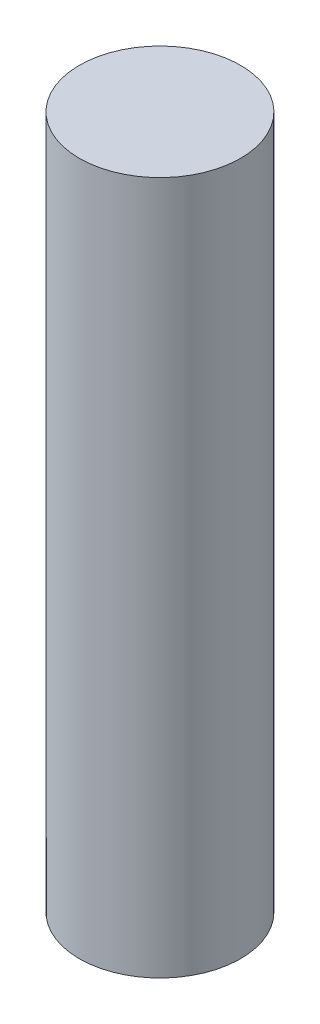
SolidWorks part; units mm, degrees
material "Plain Carbon Steel"
ref_plane "Front Plane" through (0, 0, 0) normal (0, 0, 1) x (1, 0, 0)
ref_plane "Top Plane" through (0, 0, 0) normal (0, 1, 0) x (1, 0, 0)
ref_plane "Right Plane" through (0, 0, 0) normal (1, 0, 0) x (0, 0, -1)
sketch "Sketch1" plane through (0, 0, 0) normal (0, 1, 0) x (1, 0, 0)
  circle A0 centre (0, 0) radius 10
  dimension "D1" = 20
extrude "Boss-Extrude1" add sketch "Sketch1" along normal blind 86
